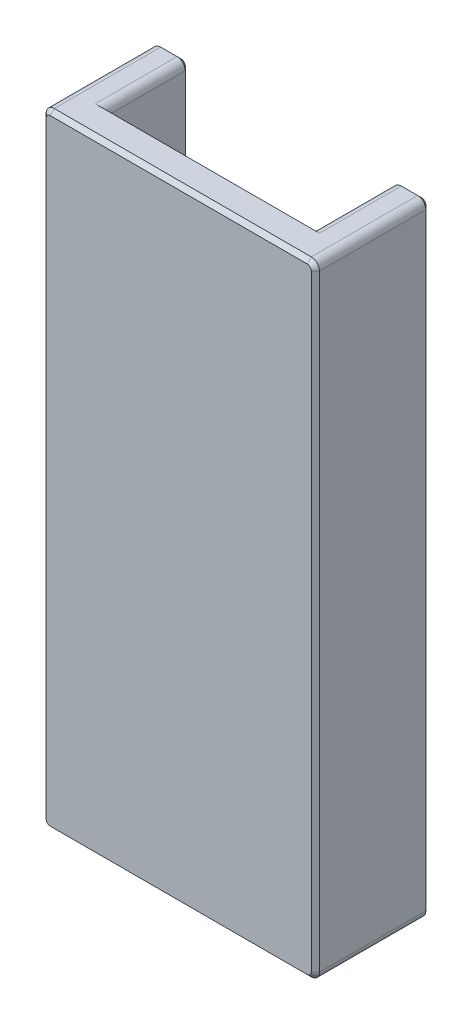
SolidWorks part; units mm, degrees
material "ABS"
ref_plane "Front Plane" through (0, 0, 0) normal (0, 0, 1) x (1, 0, 0)
ref_plane "Top Plane" through (0, 0, 0) normal (0, 1, 0) x (1, 0, 0)
ref_plane "Right Plane" through (0, 0, 0) normal (1, 0, 0) x (0, 0, -1)
sketch "Sketch1" plane through (0, 0, 0) normal (0, 0, 1) x (1, 0, 0)
  line L0 (-12.7, -25.4) -> (-12.7, 50.8)
  line L1 (-16.7, -25.4) -> (16.7, -25.4)
  line L2 (-16.7, -25.4) -> (-16.7, 50.8)
  line L3 (-16.7, 50.8) -> (16.7, 50.8)
  line L4 (16.7, -25.4) -> (16.7, 50.8)
  line L5 (0, 50.8) -> (0, -25.4) construction
  line L6 (-16.7, 12.7) -> (16.7, 12.7) construction
  line L7 (12.7, -25.4) -> (12.7, 50.8)
  line L8 (-12.7, -127) -> (-12.7, 127) construction
  line L9 (12.7, -127) -> (12.7, 127) construction
  line L10 (15.7, -25.4) -> (13.7, -25.4) construction
  line L11 (-12.7, 50.8) -> (12.7, 50.8) construction
  point P0 (0, 12.7)
  dimension "D1" = 4
extrude "Boss-Extrude1" add sketch "Sketch1" along normal blind 4 contours L1 L7 L3 L0 | L7 L1 L4 L3 | L3 L2 L1 L0 region at (-14.7, 12.7, 0) region at (0, 12.7, 0) region at (14.7, 12.7, 0)
extrude "Boss-Extrude2" add sketch "Sketch1<3>" against normal blind 10 contours L3 L2 L1 L0 | L7 L1 L4 L3 region at (-14.7, 12.7, 0) region at (14.7, 12.7, 0)
sketch "Sketch1<3>" plane through (0, 0, 0) normal (0, 0, 1) x (1, 0, 0) same geometry as "Sketch1"
fillet "Fillet1" radius 1 8 edges at (12.7, 50.8, -5) (-12.7, 50.8, -5) (-12.7, -25.4, -5) (12.7, -25.4, -5) (-16.7, -25.4, -3) (16.7, -25.4, -3) (16.7, 50.8, -3) (-16.7, 50.8, -3)
chamfer "Chamfer1" distance 0.5 angle 45 26 edges at (-16.4071, 50.5071, 4) (0, 50.8, 4) (16.4071, 50.5071, 4) (16.7, 12.7, 4) (16.4071, -25.1071, 4) (0, -25.4, 4) (-16.4071, -25.1071, 4) (-16.7, 12.7, 4) (-16.4071, 50.5071, -10) (-16.7, 12.7, -10) (-16.4071, -25.1071, -10) (-14.7, -25.4, -10) (-12.9929, -25.1071, -10) (-12.7, 12.7, -10) (-12.9929, 50.5071, -10) (-14.7, 50.8, -10) (12.9929, -25.1071, -10) (14.7, -25.4, -10) (16.4071, -25.1071, -10) (16.7, 12.7, -10) (16.4071, 50.5071, -10) (14.7, 50.8, -10) (12.9929, 50.5071, -10) (12.7, 12.7, -10) (0, 50.8, 0) (0, -25.4, 0)
